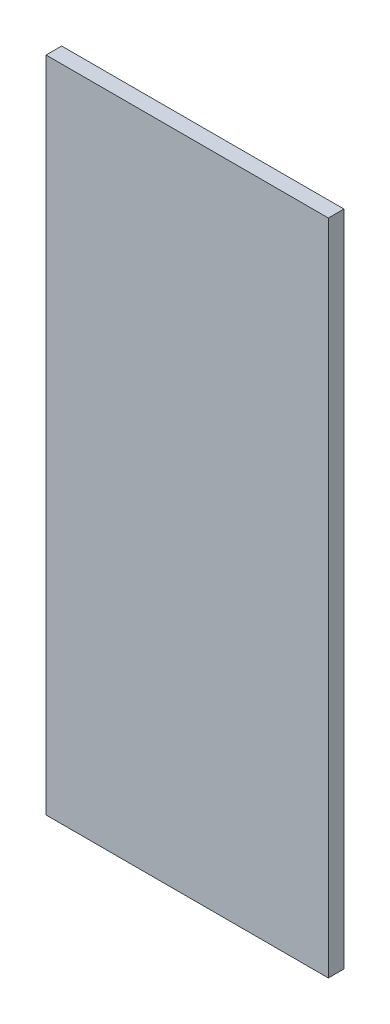
SolidWorks part; units mm, degrees
material "Perspex (TM) GS Acrylic Cast Sheet"
ref_plane "Front Plane" through (0, 0, 0) normal (0, 0, 1) x (1, 0, 0)
ref_plane "Top Plane" through (0, 0, 0) normal (0, 1, 0) x (1, 0, 0)
ref_plane "Right Plane" through (0, 0, 0) normal (1, 0, 0) x (0, 0, -1)
sketch "Sketch1" plane through (0, 0, 0) normal (0, 0, 1) x (1, 0, 0)
  line L1 (-81.5, -190) -> (81.5, -190)
  line L2 (-81.5, -190) -> (-81.5, 190)
  line L3 (-81.5, 190) -> (81.5, 190)
  line L4 (81.5, -190) -> (81.5, 190)
  line L5 (-81.5, -190) -> (81.5, 190) construction
  line L6 (-81.5, 190) -> (81.5, -190) construction
  point P0 (0, 0)
  dimension "D1" = 163
  dimension "D2" = 380
extrude "Boss-Extrude1" add sketch "Sketch1" along normal blind 9
equation "\"PCLength\"= 145mm'Length across I/O from PS to GPU"
equation "\"PCWidth\"= 340mm'Distance of longest part parallel to GPU(ussually GPU)"
equation "\"PCHeight\"= 180mm'Tallest point with mobo laying flat"
equation "\"WallThickness\"= 9mm'Thickness of each outer tank wall"
equation "\"ThermoBarrierThickness\"= 6mm'Thickness of barrier between hot side and cold side"
equation "\"HotSideGap\"= 36mm'Space in the hot side for a pump"
equation "\"PCClearance\"= 40mm'Clearance from top of tank to top of PC"
equation "\"RadiatorHeight\"= 275mm'Final Height from ground of radiators"
equation "\"D1@Sketch1\"=\"PCLength\" + (2 * \"WallThickness\")"
equation "\"D2@Sketch1\"=\"PCWidth\" + \"PCClearance\""
equation "\"D1@Boss-Extrude1\"=\"WallThickness\""
